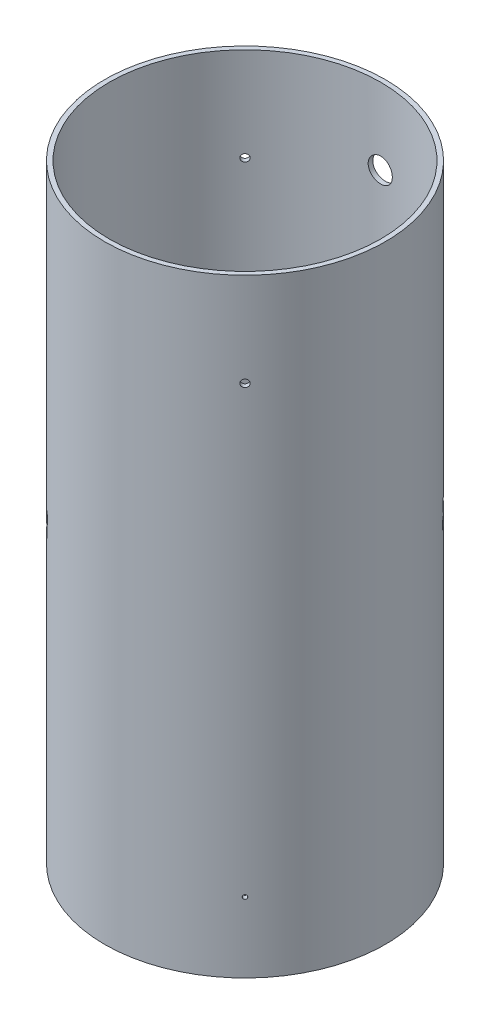
SolidWorks part; units mm, degrees
material "A-Glass Fiber"
ref_plane "Front Plane" through (0, 0, 0) normal (0, 0, 1) x (1, 0, 0)
ref_plane "Top Plane" through (0, 0, 0) normal (0, 1, 0) x (1, 0, 0)
ref_plane "Right Plane" through (0, 0, 0) normal (1, 0, 0) x (0, 0, -1)
sketch "Sketch1" plane through (0, 0, 0) normal (0, 1, 0) x (1, 0, 0)
  circle A0 centre (0, 0) radius 76.1746
  circle A1 centre (0, 0) radius 73.66
  dimension "D1" = 152.3492
  dimension "D2" = 147.32
extrude "Boss-Extrude1" add sketch "Sketch1" along normal blind 330.2
sketch "Sketch4" plane through (0, 0, 0) normal (0, 0, 1) x (1, 0, 0)
  line L0 (-76.1746, 0) -> (76.1746, 0) construction
  line L1 (76.1746, 330.2) -> (-76.1746, 330.2) construction
  line L2 (0, 330.2) -> (0, 0) construction
  line L3 (73.66, 330.2) -> (-73.66, 330.2) construction
  point P0 (0, 41.275)
  point P3 (0, 288.925)
  dimension "D1" = 41.275
  dimension "D2" = 41.275
hole_wizard "1/2 Clearance Hole5" positions "Sketch16" profile "Sketch17" hole size "1/2" standard "ANSI Inch"
sketch "Sketch16" plane through (0, 0, 0) normal (0, 0, 1) x (1, 0, 0)
  point P0 (0, 288.925)
sketch "Sketch17" plane through (0, 288.925, 0) normal (1, 0, 0) x (0, -1, 0)
  line L0 (0, 0) -> (0, 80.1345)
  line L1 (0, 80.1345) -> (6.5481, 76.2)
  line L2 (6.5481, 76.2) -> (6.5481, 0)
  line L5 (6.5481, 0) -> (0, 0)
  line L10 (0, 80.1345) -> (-6.5481, 76.2) construction
  line L11 (0, -6.35) -> (0, 107.95) construction
  dimension "Hole Dia." = 13.0962
  dimension "Hole Depth" = 76.2
  dimension "Drill Angle" = 118
hole_wizard "1/2 Clearance Hole7" positions "Sketch20" profile "Sketch21" hole size "1/2" standard "ANSI Inch"
sketch "Sketch20" plane through (0, 0, 0) normal (0, 0, 1) x (1, 0, 0)
  point P0 (0, 41.275)
sketch "Sketch21" plane through (0, 41.275, 0) normal (1, 0, 0) x (0, -1, 0)
  line L0 (0, 0) -> (0, 80.1345)
  line L1 (0, 80.1345) -> (6.5481, 76.2)
  line L2 (6.5481, 76.2) -> (6.5481, 0)
  line L5 (6.5481, 0) -> (0, 0)
  line L10 (0, 80.1345) -> (-6.5481, 76.2) construction
  line L11 (0, -6.35) -> (0, 107.95) construction
  dimension "Hole Dia." = 13.0962
  dimension "Hole Depth" = 76.2
  dimension "Drill Angle" = 118
ref_plane "Plane1" through (0, 0, 0) normal (-0.7071, 0, 0.7071) x (0.7071, 0, 0.7071)
sketch "Sketch23" plane through (0, 0, 0) normal (-0.7071, 0, 0.7071) x (0.7071, 0, 0.7071)
  line L0 (0, 0) -> (0, 330.2) construction
  line L1 (73.66, 330.2) -> (-73.66, 330.2) construction
  line L2 (-76.1746, 165.1) -> (76.1746, 165.1) construction
  line L3 (76.1746, 0) -> (76.1746, 330.2) construction
  circle A1 centre (0, 38.1) radius 1.0922
  point P12 (0, 165.1)
  dimension "D2" = 127
extrude "Shear Scrrews" cut sketch "Sketch23" against normal through all
pattern_circular "CirPattern1" count 4 over 360 about axis through (0, 330.2, 0) along (0, -1, 0) of "Shear Scrrews"
ref_plane "Camera Cutout Plane" through (0, 0, 0) normal (0.7071, 0, -0.7071) x (0, -1, 0)
hole_wizard "Ø4.0 (4) Diameter Hole - Forward Tube Secure" positions "Sketch30" profile "Sketch31" hole size "Ø4.0" standard "ANSI Metric"
sketch "Sketch30" plane through (0, 0, 0) normal (0.7071, 0, -0.7071) x (0, -1, 0)
  line L0 (-330.2, 76.1746) -> (-330.2, -76.1746) construction
  line L1 (-330.2, 0) -> (0, 0) construction
  point P0 (-279.4, 0)
  dimension "D1" = 50.8
sketch "Sketch31" plane through (0, 279.4, 0) normal (0, 1, 0) x (0.7071, 0, 0.7071)
  line L0 (0, 0) -> (0, 90.1017)
  line L1 (0, 90.1017) -> (2, 88.9)
  line L2 (2, 88.9) -> (2, 0)
  line L5 (2, 0) -> (0, 0)
  line L10 (0, 90.1017) -> (-2, 88.9) construction
  line L11 (0, -6.35) -> (0, 107.95) construction
  dimension "Hole Dia." = 4
  dimension "Hole Depth" = 88.9
  dimension "Drill Angle" = 118
sketch "Sketch26" plane through (0, 0, 0) normal (0.7071, 0, -0.7071) x (0, -1, 0)
  line L0 (-330.2, 0) -> (0, 0) construction
  line L1 (-174.625, -5) -> (-167.625, -5)
  line L2 (-174.625, -5) -> (-174.625, 5)
  line L3 (-174.625, 5) -> (-167.625, 5)
  line L4 (-167.625, -5) -> (-167.625, 5)
  line L5 (-174.625, -5) -> (-167.625, 5) construction
  line L6 (-174.625, 5) -> (-167.625, -5) construction
  line L7 (-330.2, 76.1746) -> (-330.2, -76.1746) construction
  circle A0 centre (-158.735, 0) radius 2.75
  point P0 (-171.125, 0)
  dimension "D4" = 5.5
  dimension "D1" = 7
  dimension "D2" = 10
  dimension "D3" = 155.575
  dimension "D5" = 8.89
extrude "Upwards Camera Cutout" cut sketch "Sketch26" along normal through all
sketch "Sketch27" plane through (0, 0, 0) normal (0.7071, 0, -0.7071) x (0, -1, 0)
  line L0 (-330.2, 0) -> (0, 0) construction
  line L1 (-155.575, 5) -> (-162.575, 5)
  line L2 (-155.575, 5) -> (-155.575, -5)
  line L3 (-155.575, -5) -> (-162.575, -5)
  line L4 (-162.575, 5) -> (-162.575, -5)
  line L5 (-155.575, 5) -> (-162.575, -5) construction
  line L6 (-155.575, -5) -> (-162.575, 5) construction
  line L8 (0, -76.1746) -> (0, 76.1746) construction
  circle A0 centre (-171.465, 0) radius 2.75
  point P0 (-159.075, 0)
  dimension "D4" = 5.5
  dimension "D1" = 7
  dimension "D2" = 10
  dimension "D3" = 8.89
  dimension "D5" = 155.575
extrude "Downwards Camera Cutout" cut sketch "Sketch27" against normal through all
ref_plane "Camera Side Hole Plane" through (0, 0, 0) normal (0.7567, 0, -0.6537) x (0, -1, 0)
sketch "Sketch28" plane through (0, 0, 0) normal (0.7567, 0, -0.6537) x (0, -1, 0)
  line L0 (-330.2, 0) -> (0, 0) construction
  line L1 (-162.575, -10.5216) -> (-162.575, -0.5482) construction
  circle A0 centre (-166.385, 0) radius 2.75
  dimension "D1" = 5.5
  dimension "D2" = 3.81
extrude "Cut-Extrude4" cut sketch "Sketch28" against normal through all
pattern_circular "CirPattern3" count 2 every 8.407 about axis through (0, 0, 0) along (0, 1, 0) of "Cut-Extrude4"
sketch "Sketch29" plane through (0, 0, 0) normal (0.7567, 0, -0.6537) x (0, -1, 0)
  line L0 (-330.2, 0) -> (0, 0) construction
  line L1 (-167.625, 10.3381) -> (-167.625, 0.3647) construction
  circle A0 centre (-163.815, 0) radius 2.75
  dimension "D1" = 5.5
  dimension "D2" = 3.81
extrude "Cut-Extrude5" cut sketch "Sketch29" along normal through all
pattern_circular "CirPattern4" count 2 every 8.407 about axis through (0, 330.2, 0) along (0, 1, 0) of "Cut-Extrude5"
pattern_circular "CirPattern5" count 4 over 360 about axis through (0, 330.2, 0) along (0, 1, 0) of "Ø4.0 (4) Diameter Hole - Forward Tube Secure"
equation "\"Mid_Coupler_Length\" = 13in"
equation "\"D1@Boss-Extrude1\"=\"Mid_Coupler_Length\""
equation "\"Shear_Screw_Coupler_Location\" = 4.5in"
equation "\"Shear_Screw_Diameter\" = 0.086in"
equation "\"D2@Sketch23\"=\"Shear_Screw_Coupler_Location\"+0.5"
equation "\"Mid_Tube_Length\"= 1in"
equation "\"Bodytube_OD\" = 6.17in"
equation "\"Bodytube_ID\" = 5.998in"
equation "\"Camera_Cutout_Width\"=10mm"
equation "\"Camera_Cutout_Height\"=7mm"
equation "\"Fwd_Tube_Length\" = 40in"
equation "\"BKHD_Screw_Diam\"= 3.5mm"
equation "\"Fwd_BKHD_From_Top\" = 18in"
equation "\"Motor_OD\" = 4in"
equation "\"Aft_Section_Length\"= 39in"
equation "\"AB_Coupler_OD_Length\"= 1in"
equation "\"AB_Coupling_Section_Length\"= 0.375in"
equation "\"AB_Coupler_Length\"= \"AB_Coupler_OD_Length\" + \"AB_Coupling_Section_Length\" * 2"
equation "\"Cutout_Angle\" = 80"
equation "\"AB_Paddle_Height\" = 0.375in"
equation "\"AB_Coupler_Num_Screws\"= 4"
equation "\"AB_BKHD_Thickness\" = 0.375in"
equation "\"AB_Mount_From_Bottom\" = 23.175in"
equation "\"Num_Cutouts\" = 3"
equation "\"AB_Coupler_OD\"= 6.17in"
equation "\"AB_Coupler_ID\"= 5.75in"
equation "\"AB_Coupler_Surface_Diameter\"= 5.998in"
equation "\"AB_Coupling_Screw_Diameter\"= 0.15748in"
equation "\"AB_Central_Bushing_Length\" = .4724in"
equation "\"Lead_Screw_Dist\" = 3.4in"
equation "\"Lead_Screw_Diam\" = 0.386in"
equation "\"Lead_Screw_Length\" = (\"Mid_Coupler_Length\" + 2*0.375in + 2*0.5in)"
equation "\"Paddle_Pin_Offset\" = .25in"
equation "\"Paddle_Pin_Radius\" = 2.25in"
equation "\"SS_Paddle_Pin_Radius\" = 2.25*0.66in"
equation "\"Paddle_Gear_OD\" = 3.2in"
equation "\"Drive_Gear_OD\" = 1.7in"
equation "\"Fin_Thickness\"= .118in"
equation "\"Guiderail_Cutout_Diameter\"= 1.5in"
equation "\"DB9_Hole_Dist\" = 25mm"
equation "\"DB9_Relief_Width\" = 0.47in"
equation "\"DB9_Relief_Hole_Offset\" = 0.09in"
equation "\"Airbrakes_Wire_Hole_Dia\" = .25in"
equation "\"Airbrakes_Wire_Hole_Dist\" = 1.1in"
equation "\"Servo_Gear_Offset\" = 0.5in"
equation "\"FWD_Shear_Screw_Dist\" = 1.5in"
equation "\"Camera_Screw_Dia\" = 0.216535"
equation "\"Camera_Hole_Angle\" = atn ( 2 / 3 * tan ( 12.5deg ) )"
equation "\"D1@Sketch26\"=\"Camera_Cutout_Height\""
equation "\"D2@Sketch26\"=\"Camera_Cutout_Width\""
equation "\"D3@Sketch26\"=6.125"
equation "\"D1@Sketch27\"=\"Camera_Cutout_Height\""
equation "\"D2@Sketch27\"=\"Camera_Cutout_Width\""
equation "\"D1@Sketch28\"=\"Camera_Screw_Dia\""
equation "\"D2@CirPattern3\"=\"Camera_Hole_Angle\""
equation "\"D1@Sketch29\"=\"Camera_Screw_Dia\""
equation "\"D2@CirPattern4\"=\"Camera_Hole_Angle\""
equation "\"Coupler_OD\" = 5.998"
equation "\"D1@Sketch1\"=\"Coupler_OD\""
equation "\"Coupler_ID\" = 5.8"
equation "\"D2@Sketch1\"=\"Coupler_ID\""
